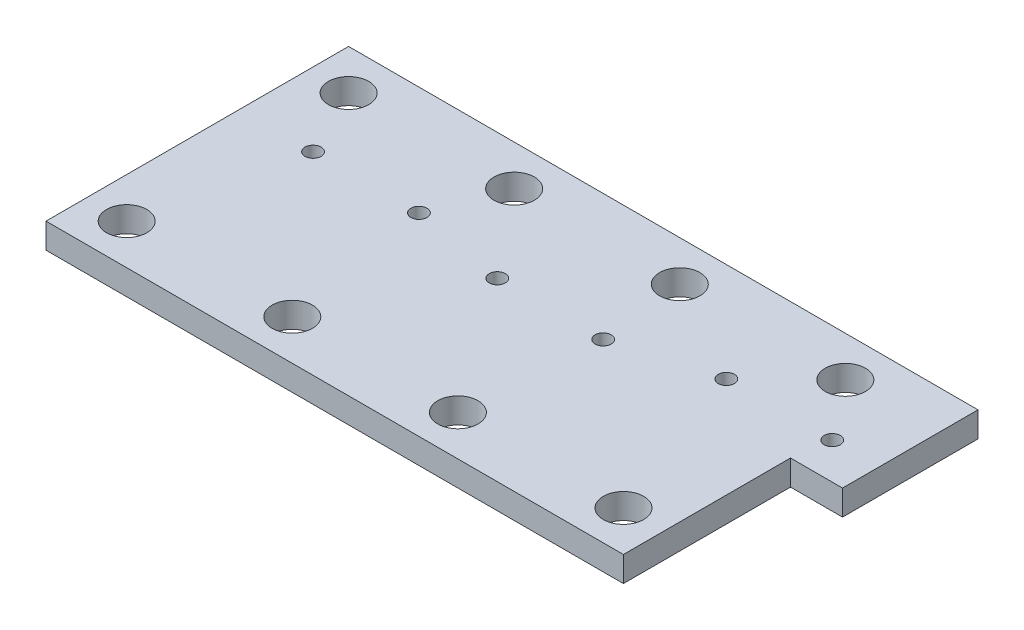
SolidWorks part; units mm, degrees
material "K110"
ref_plane "Front Plane" through (0, 0, 0) normal (0, 0, 1) x (1, 0, 0)
ref_plane "Top Plane" through (0, 0, 0) normal (0, 1, 0) x (1, 0, 0)
ref_plane "Right Plane" through (0, 0, 0) normal (1, 0, 0) x (0, 0, -1)
sketch "Sketch1" plane through (0, 0, 0) normal (0, 1, 0) x (1, 0, 0)
  line L0 (-229, 60) -> (-229, -60) construction
  line L1 (-229, -60) -> (0, -60)
  line L2 (-229, -60) -> (-229, 60)
  line L3 (-229, 60) -> (0, 60)
  line L4 (0, -60) -> (0, 60)
  point P4 (0, 0)
  dimension "D1" = 120
extrude "Boss-Extrude1" add sketch "Sketch1" along normal mid plane 10
sketch "Sketch4" plane through (0, 5, 0) normal (0, 1, 0) x (1, 0, 0)
  line L1 (0, 60) -> (20.6325, 60)
  line L2 (0, 60) -> (0, 6.27)
  line L3 (0, 6.27) -> (20.6325, 6.27)
  line L4 (20.6325, 60) -> (20.6325, 6.27)
extrude "Boss-Extrude2" add sketch "Sketch4" against normal up to surface (10 mm away) up to face at (-114.5, -5, 0)
hole_wizard "Ø16.0 (16) Diameter Hole1" positions "Sketch7" profile "Sketch6" hole size "Ø16.0" standard "ISO" end condition through all
sketch "Sketch7" plane through (0, 5, 0) normal (0, 1, 0) x (1, 0, 0)
  point P0 (-213, 44)
  point P3 (-147.323, 44)
  point P6 (-81.646, 44)
  point P9 (-15.969, 44)
  point P12 (-213, -44)
  point P15 (-147.323, -44)
  point P18 (-81.646, -44)
  point P21 (-15.969, -44)
sketch "Sketch6" plane through (-213, 5, -44) normal (1, 0, 0) x (0, 0, 1)
  line L0 (0, 0) -> (0, 10)
  line L1 (0, 10) -> (8, 10)
  line L2 (8, 10) -> (8, 0)
  line L5 (8, 0) -> (0, 0)
  line L11 (0, -6.35) -> (0, 107.95) construction
  dimension "Thru Hole Dia." = 16
  dimension "Thru Hole Depth" = 10
hole_wizard "M6 Clearance Hole1" positions "Sketch12" profile "Sketch11" hole size "M6" standard "ISO" end condition through all
sketch "Sketch12" plane through (0, 5, 0) normal (0, 1, 0) x (1, 0, 0)
  point P0 (-199.875, 16.78)
  point P3 (-157.875, 16.78)
  point P6 (-119.875, 9.8524)
  point P9 (-77.875, 9.8524)
  point P12 (-39.875, 20.691)
  point P15 (2.125, 20.691)
sketch "Sketch11" plane through (-199.875, 5, -16.78) normal (1, 0, 0) x (0, 0, 1)
  line L0 (0, 0) -> (0, 10)
  line L1 (0, 10) -> (3.2, 10)
  line L2 (3.2, 10) -> (3.2, 0)
  line L5 (3.2, 0) -> (0, 0)
  line L11 (0, -6.35) -> (0, 107.95) construction
  dimension "Thru Hole Dia." = 6.4
  dimension "Thru Hole Depth" = 10
